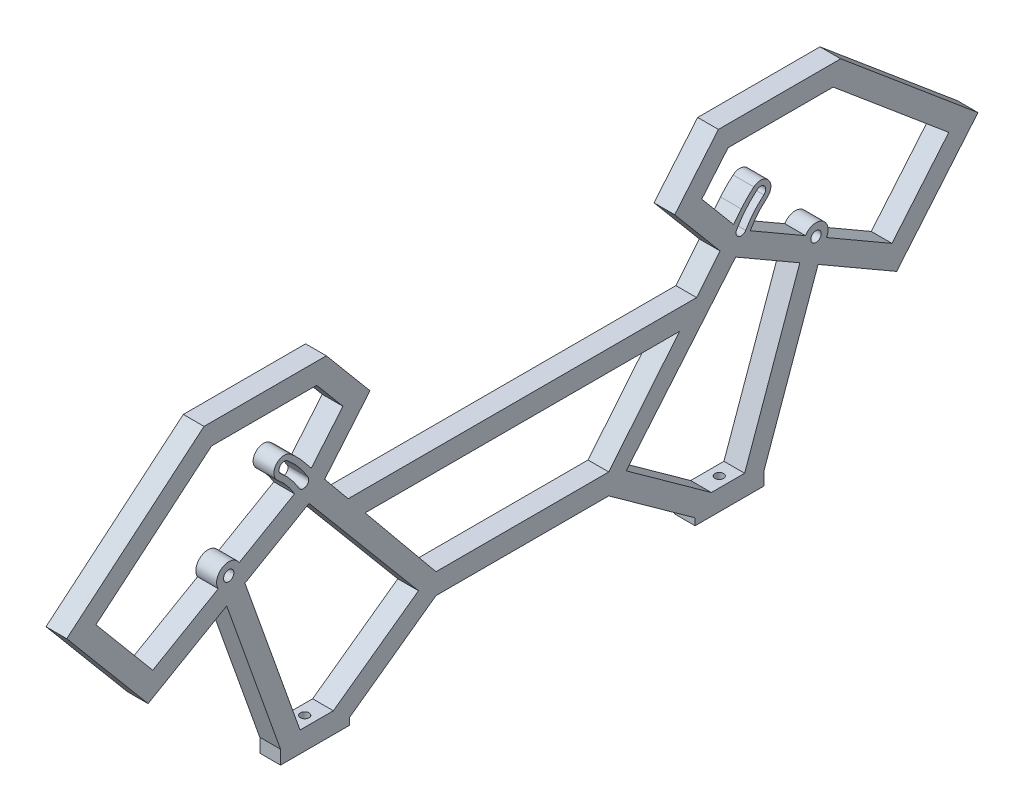
SolidWorks part; units mm, degrees
material "1060 Alloy"
ref_plane "Front Plane" through (0, 0, 0) normal (0, 0, 1) x (1, 0, 0)
ref_plane "Top Plane" through (0, 0, 0) normal (0, 1, 0) x (1, 0, 0)
ref_plane "Right Plane" through (0, 0, 0) normal (1, 0, 0) x (0, 0, -1)
sketch "Sketch1" plane through (0, 0, 0) normal (1, 0, 0) x (0, 0, -1)
  line L0 (65.8489, 71.0697) -> (85, 55) construction
  line L1 (50, 0) -> (70, 0)
  line L2 (131.2449, 61.8851) -> (104.8907, 30.4773) construction
  line L3 (131.2449, 61.8851) -> (73.0256, 110.737) construction
  line L4 (104.8907, 30.4773) -> (46.6713, 79.3292) construction
  line L5 (73.0256, 110.737) -> (46.6713, 79.3292) construction
  line L6 (50, 0) -> (50, 2)
  line L7 (50, 2) -> (25, 20)
  line L8 (25, 20) -> (0, 20)
  line L9 (120.803, 46.5093) -> (61.0516, 96.6468) construction
  line L10 (0, 20) -> (0, 26)
  line L11 (0, 26) -> (25, 26)
  line L12 (25, 26) -> (45.5054, 51)
  line L13 (45.5054, 51) -> (0, 51)
  line L14 (65.0961, 75.6176) -> (85.3963, 58.5837) construction
  line L15 (65.0961, 75.6176) -> (82.13, 95.9178) construction
  line L16 (85.3963, 58.5837) -> (102.4301, 78.8839) construction
  line L17 (0, 51) -> (0, 57)
  line L18 (82.13, 95.9178) -> (102.4301, 78.8839) construction
  line L19 (0, 57) -> (50.4267, 57)
  line L20 (106.773, 98) -> (-82.0096, 98) construction
  line L21 (44.0994, 80.9313) -> (57.2251, 65.2887)
  line L22 (68.9303, 74.1511) -> (85, 55) construction
  line L23 (85, 55) -> (63.3494, 67.5) construction
  line L24 (30.0596, 23.7505) -> (61.7373, 61.5025)
  line L25 (61.7373, 61.5025) -> (80.3101, 50.7795)
  line L26 (80.3101, 50.7795) -> (64.3431, 6)
  line L27 (64.3431, 6) -> (54.7131, 6)
  line L28 (54.7131, 6) -> (30.0596, 23.7505)
  line L29 (70, 0) -> (70, 4)
  line L30 (70, 4) -> (85.5926, 47.7296)
  line L31 (85.5926, 47.7296) -> (108.3447, 34.5937)
  line L32 (108.3447, 34.5937) -> (131.8877, 62.6512)
  line L33 (131.8877, 62.6512) -> (92.1442, 96)
  line L34 (92.1442, 96) -> (56.7435, 96)
  line L35 (132, 92.0287) -> (132, -4.4174) construction
  line L36 (59.5414, 90) -> (51.9319, 80.9313)
  line L37 (140, 92.0287) -> (140, -4.4174) construction
  line L38 (88.0311, 53.25) -> (106.9846, 42.3072)
  line L39 (65.9474, 66) -> (81.9689, 56.75)
  line L42 (106.9846, 42.3072) -> (123.4347, 61.9116)
  line L43 (123.4347, 61.9116) -> (89.9603, 90)
  line L44 (89.9603, 90) -> (59.5414, 90)
  line L46 (56.7435, 96) -> (44.0994, 80.9313)
  line L47 (61.7373, 61.5025) -> (59.4392, 63.4309) construction
  line L48 (59.4392, 63.4309) -> (65.8489, 71.0697) construction
  line L49 (85, 55) -> (75.9689, 29.6723) construction
  line L50 (57.2251, 65.2887) -> (50.4267, 57)
  line L51 (51.9319, 80.9313) -> (61.0968, 70.009)
  line L52 (61.0968, 70.009) -> (63.3508, 72.757)
  circle A0 centre (85, 55) radius 1.5
  circle A1 centre (65.8489, 71.0697) radius 1.5 construction
  circle A2 centre (85, 55) radius 3 construction
  circle A3 centre (65.8489, 71.0697) radius 3 construction
  arc A4 (63.3494, 67.5) -> (68.9303, 74.1511) centre (85, 55) cw construction
  arc A5 (67.9661, 75.3002) -> (62.0503, 68.25) centre (85, 55) ccw
  arc A6 (69.8945, 73.002) -> (64.6484, 66.75) centre (85, 55) ccw
  arc A7 (69.8945, 73.002) -> (67.9661, 75.3002) centre (68.9303, 74.1511) ccw
  arc A8 (62.0503, 68.25) -> (64.6484, 66.75) centre (63.3494, 67.5) ccw
  arc A9 (70.8587, 71.853) -> (65.9474, 66) centre (85, 55) ccw
  arc A10 (63.3508, 72.757) -> (67.0019, 76.4492) centre (85, 55) cw
  arc A11 (67.0019, 76.4492) -> (70.8587, 71.853) centre (68.9303, 74.1511) cw
  arc A12 (81.9689, 56.75) -> (88.0311, 53.25) centre (85, 55) cw
  point P25 (65.8489, 71.0697)
  dimension "D14" = 3
  dimension "D16" = 1.5
  dimension "D21" = 1.5
  dimension "D29" = 6
  dimension "D30" = 1.5
  dimension "D19" = 3.5
  dimension "D1" = 6
  dimension "D2" = 31
  dimension "D3" = 3
  dimension "D4" = 41
  dimension "D5" = 20
  dimension "D6" = 55
  dimension "D7" = 85
  dimension "D8" = 25
  dimension "D9" = 20
  dimension "D10" = 40
  dimension "D11" = 50
  dimension "D12" = 26.5
  dimension "D13" = 26.5
  dimension "D15" = 3.5
  dimension "D17" = 10
  dimension "D18" = 6
  dimension "D20" = 132
  dimension "D22" = 3
  dimension "D23" = 3
  dimension "D24" = 140
  dimension "D26" = 5
  dimension "D27" = 2
  dimension "D28" = 98
  dimension "D31" = 6
  dimension "D32" = 6
  dimension "D33" = 6
  dimension "D34" = 6
  dimension "D35" = 6
  dimension "D36" = 6
  dimension "D37" = 3
  dimension "D38" = 6
  dimension "D39" = 6
  dimension "D40" = 20
  dimension "D41" = 6
  dimension "D42" = 25
  dimension "D43" = 6
  dimension "D44" = 2
  dimension "D45" = 4
  dimension "D46" = 25
extrude "Boss-Extrude1" add sketch "Sketch1" along normal blind 6
hole_wizard "Tap Drill for M3 Tap1" positions "Sketch3" profile "Sketch2" hole size "M3" standard "ISO"
sketch "Sketch3" plane through (0, 0, 0) normal (0, -1, 0) x (-1, 0, 0)
  line L1 (-6, 50) -> (-6, 70) construction
  line L2 (-6, 70) -> (0, 70) construction
  point P0 (-3, 60)
  dimension "D1" = 10
  dimension "D2" = 3
sketch "Sketch2" plane through (3, 0, -60) normal (1, 0, 0) x (0, 0, -1)
  line L0 (0, 0) -> (0, 10.7511)
  line L1 (0, 10.7511) -> (1.25, 10)
  line L2 (1.25, 10) -> (1.25, 0)
  line L5 (1.25, 0) -> (0, 0)
  line L10 (0, 10.7511) -> (-1.25, 10) construction
  line L11 (0, -6.35) -> (0, 107.95) construction
  dimension "Hole Dia." = 2.5
  dimension "Hole Depth" = 10
  dimension "Drill Angle" = 118
mirror "Mirror1" about plane through (0, 0, 0) normal (0, 0, 1) of "Boss-Extrude1", "Tap Drill for M3 Tap1"
